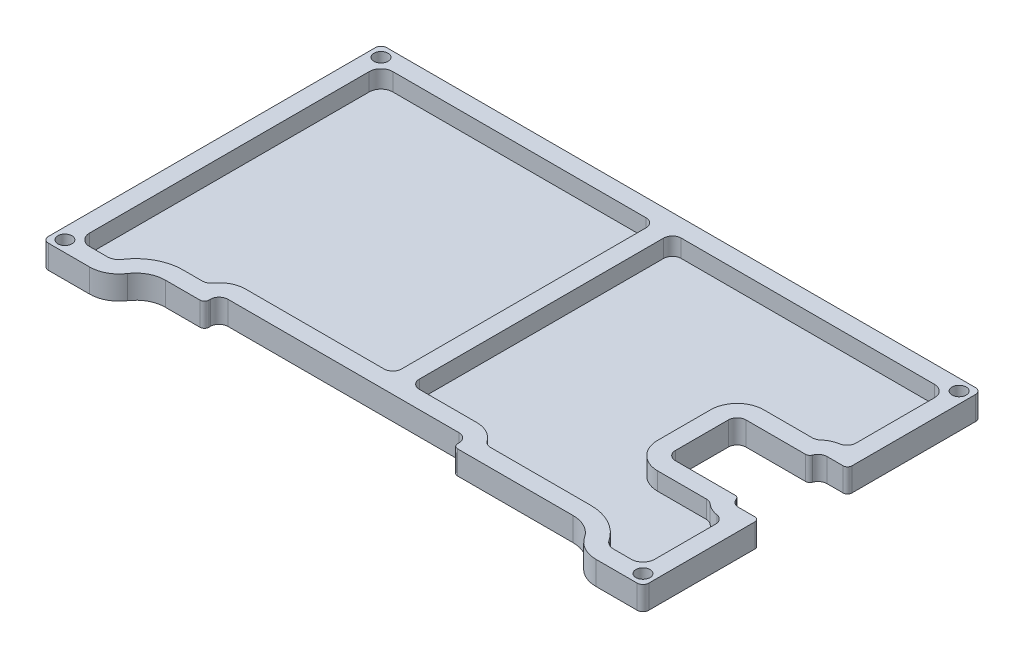
SolidWorks part; units mm, degrees
ref_plane "Ebene vorne" through (0, 0, 0) normal (0, 0, 1) x (1, 0, 0)
ref_plane "Ebene oben" through (0, 0, 0) normal (0, 1, 0) x (1, 0, 0)
ref_plane "Ebene rechts" through (0, 0, 0) normal (1, 0, 0) x (0, 0, -1)
sketch "Skizze1" plane through (0, 0, 0) normal (0, 1, 0) x (1, 0, 0)
  line L1 (-49.1, -26.85) -> (49.1, -26.85) construction
  line L2 (-49.1, -26.85) -> (-49.1, 26.85) construction
  line L3 (-49.1, 26.85) -> (49.1, 26.85) construction
  line L4 (49.1, -26.85) -> (49.1, 26.85) construction
  line L5 (-49.1, -26.85) -> (49.1, 26.85) construction
  line L6 (-49.1, 26.85) -> (49.1, -26.85) construction
  line L7 (-51, -28.75) -> (51, -28.75)
  line L8 (-51, -28.75) -> (-51, 28.75)
  line L9 (-51, 28.75) -> (51, 28.75)
  line L10 (51, -28.75) -> (51, 28.75)
  line L11 (-51, -28.75) -> (51, 28.75) construction
  line L12 (-51, 28.75) -> (51, -28.75) construction
  point P0 (0, 0)
  point P6 (0, 0)
  dimension "D1" = 102
  dimension "D2" = 57.5
  dimension "D3" = 98.2
  dimension "D4" = 53.7
extrude "Aufsatz-Linear austragen1" add sketch "Skizze1" along normal blind 1
fillet "Verrundung1" radius 1 4 edges at (51, 0.5, -28.75) (51, 0.5, 28.75) (-51, 0.5, 28.75) (-51, 0.5, -28.75)
sketch "Skizze5" plane through (0, 1, 0) normal (0, 1, 0) x (1, 0, 0)
  line L0 (-43, -28.75) -> (43, -28.75)
  line L1 (-50, -28.75) -> (50, -28.75) construction
  line L2 (-51, 27.75) -> (-51, -27.75) construction
  line L3 (34.6484, -24.25) -> (-34.6484, -24.25)
  line L4 (51, -27.75) -> (51, 27.75) construction
  arc A0 (-38.8242, -26.5) -> (-43, -28.75) centre (-43, -23.75) cw
  arc A1 (-38.8242, -26.5) -> (-34.6484, -24.25) centre (-34.6484, -29.25) cw
  arc A2 (38.8242, -26.5) -> (34.6484, -24.25) centre (34.6484, -29.25) ccw
  arc A3 (43, -28.75) -> (38.8242, -26.5) centre (43, -23.75) cw
  dimension "D3" = 5
  dimension "D1" = 8
  dimension "D2" = 8
  dimension "D4" = 4.5
extrude "Schnitt-Linear austragen1" cut sketch "Skizze5" against normal up to next
sketch "Skizze6" plane through (0, 1, 0) normal (0, 1, 0) x (1, 0, 0)
  line L0 (14.25, -21.75) -> (-28, -21.75)
  line L2 (-28, -21.75) -> (-28, -24.25)
  line L3 (-28, -24.25) -> (14.25, -24.25)
  line L4 (14.25, -24.25) -> (14.25, -21.75)
  line L5 (51, -27.75) -> (51, 27.75) construction
  line L7 (33.75, 4.5) -> (46, 4.5)
  line L8 (51, 4.5) -> (51, -7.5)
  line L9 (46, -7.5) -> (33.75, -7.5)
  line L10 (33.75, -7.5) -> (33.75, 4.5)
  line L11 (43, -28.75) -> (50, -28.75) construction
  line L12 (-51, 27.75) -> (-51, -27.75) construction
  line L13 (34.6484, -24.25) -> (-34.6484, -24.25) construction
  line L14 (46, -7.5) -> (46, -9)
  line L15 (46, -9) -> (51, -9)
  line L16 (51, -9) -> (51, -7.5)
  line L17 (46, 4.5) -> (46, 6)
  line L18 (46, 6) -> (51, 6)
  line L19 (51, 6) -> (51, 4.5)
  line L20 (46, -7.5) -> (51, -7.5) construction
  line L21 (46, 4.5) -> (51, 4.5) construction
  dimension "D1" = 42.25
  dimension "D2" = 23
  dimension "D3" = 2.5
  dimension "D4" = 21.25
  dimension "D5" = 12
  dimension "D6" = 17.25
  dimension "D7" = 15
  dimension "D8" = 5
extrude "Schnitt-Linear austragen2" cut sketch "Skizze6" against normal up to next
fillet "Verrundung2" radius 1.5 6 edges at (33.75, 0.5, -4.5) (33.75, 0.5, 7.5) (14.25, 0.5, 21.75) (-28, 0.5, 21.75) (46, 0.5, -6) (46, 0.5, 9)
fillet "Verrundung3" radius 0.75 6 edges at (-28, 0.5, 24.25) (14.25, 0.5, 24.25) (51, 0.5, -6) (51, 0.5, 9) (46, 0.5, -4.5) (46, 0.5, 7.5)
sketch "Skizze8" plane through (0, 1, 0) normal (0, 1, 0) x (1, 0, 0)
  line L0 (35.25, 7.5) -> (44.1459, 7.5)
  line L1 (47.5, 9) -> (48, 9)
  line L2 (48, 9) -> (48, 25.75)
  line L3 (48, 25.75) -> (1.5, 25.75)
  line L4 (-48, 25.75) -> (-48, -25.75)
  line L5 (-48, -25.75) -> (-43, -25.75)
  line L6 (-34.6484, -21.25) -> (-30.5311, -21.25)
  line L7 (-30.5311, -21.25) -> (-30.5311, -21.25)
  line L8 (-26.5, -18.75) -> (-1.5, -18.75)
  line L9 (16.7811, -21.25) -> (16.7811, -21.25)
  line L10 (16.7811, -21.25) -> (34.6484, -21.25)
  line L11 (43, -25.75) -> (48, -25.75)
  line L12 (48, -25.75) -> (48, -12)
  line L13 (48, -12) -> (47.5, -12)
  line L14 (44.1459, -10.5) -> (35.25, -10.5)
  line L15 (30.75, -6) -> (30.75, 3)
  line L16 (35.25, 4.5) -> (45.3787, 4.5)
  line L17 (47.5, 6) -> (50.25, 6)
  line L18 (51, 6.75) -> (51, 27.75)
  line L19 (50, 28.75) -> (-50, 28.75)
  line L20 (-51, 27.75) -> (-51, -27.75)
  line L21 (-50, -28.75) -> (-43, -28.75)
  line L22 (-34.6484, -24.25) -> (-28.75, -24.25)
  line L23 (-28, -23.5) -> (-28, -23.25)
  line L24 (-26.5, -21.75) -> (12.75, -21.75)
  line L25 (14.25, -23.25) -> (14.25, -23.5)
  line L26 (15, -24.25) -> (34.6484, -24.25)
  line L27 (43, -28.75) -> (50, -28.75)
  line L28 (51, -27.75) -> (51, -9.75)
  line L29 (50.25, -9) -> (47.5, -9)
  line L30 (45.3787, -7.5) -> (35.25, -7.5)
  line L31 (33.75, -6) -> (33.75, 3)
  line L32 (35.25, 4.5) -> (45.3787, 4.5)
  line L33 (47.5, 6) -> (50.25, 6)
  line L34 (51, 6.75) -> (51, 27.75)
  line L35 (50, 28.75) -> (-50, 28.75)
  line L36 (-51, 27.75) -> (-51, -27.75)
  line L37 (-50, -28.75) -> (-43, -28.75)
  line L38 (-34.6484, -24.25) -> (-28.75, -24.25)
  line L39 (-28, -23.5) -> (-28, -23.25)
  line L40 (-26.5, -21.75) -> (12.75, -21.75)
  line L41 (14.25, -23.25) -> (14.25, -23.5)
  line L42 (15, -24.25) -> (34.6484, -24.25)
  line L43 (43, -28.75) -> (50, -28.75)
  line L44 (51, -27.75) -> (51, -9.75)
  line L45 (50.25, -9) -> (47.5, -9)
  line L46 (45.3787, -7.5) -> (35.25, -7.5)
  line L47 (33.75, -6) -> (33.75, 3)
  line L48 (-1.5, 25.75) -> (-1.5, -18.75)
  line L49 (1.5, 0) -> (0, 0) construction
  line L50 (0, 0) -> (-1.5, 0) construction
  line L51 (1.5, 25.75) -> (1.5, -18.75)
  line L52 (1.5, -18.75) -> (12.75, -18.75)
  line L53 (-26.5, -18.75) -> (12.75, -18.75) construction
  line L54 (-1.5, 25.75) -> (-48, 25.75)
  line L55 (48, 25.75) -> (-48, 25.75) construction
  arc A0 (44.1459, 7.5) -> (44.1459, 7.5) centre (44.1459, 7.5) ccw
  arc A1 (47.5, 9) -> (44.1459, 7.5) centre (47.5, 4.5) ccw
  arc A2 (48, 9) -> (48, 9) centre (48, 9) ccw
  arc A3 (48, 25.75) -> (48, 25.75) centre (48, 25.75) ccw
  arc A4 (-48, 25.75) -> (-48, 25.75) centre (-48, 25.75) ccw
  arc A5 (-48, -25.75) -> (-48, -25.75) centre (-48, -25.75) ccw
  arc A6 (-43, -25.75) -> (-41.3297, -24.85) centre (-43, -23.75) ccw
  arc A7 (-34.6484, -21.25) -> (-41.3297, -24.85) centre (-34.6484, -29.25) ccw
  arc A8 (-30.5311, -21.25) -> (-30.5311, -21.25) centre (-30.5311, -21.25) ccw
  arc A9 (-26.5, -18.75) -> (-30.5311, -21.25) centre (-26.5, -23.25) ccw
  arc A10 (16.7811, -21.25) -> (12.75, -18.75) centre (12.75, -23.25) ccw
  arc A11 (16.7811, -21.25) -> (16.7811, -21.25) centre (16.7811, -21.25) ccw
  arc A12 (41.3297, -24.85) -> (34.6484, -21.25) centre (34.6484, -29.25) ccw
  arc A13 (41.3297, -24.85) -> (43, -25.75) centre (43, -23.75) ccw
  arc A14 (48, -25.75) -> (48, -25.75) centre (48, -25.75) ccw
  arc A15 (48, -12) -> (48, -12) centre (48, -12) ccw
  arc A16 (44.1459, -10.5) -> (47.5, -12) centre (47.5, -7.5) ccw
  arc A17 (44.1459, -10.5) -> (44.1459, -10.5) centre (44.1459, -10.5) ccw
  arc A18 (30.75, -6) -> (35.25, -10.5) centre (35.25, -6) ccw
  arc A19 (35.25, 7.5) -> (30.75, 3) centre (35.25, 3) ccw
  arc A20 (45.3787, 4.5) -> (46.0858, 5) centre (45.3787, 5.25) ccw
  arc A21 (47.5, 6) -> (46.0858, 5) centre (47.5, 4.5) ccw
  arc A22 (50.25, 6) -> (51, 6.75) centre (50.25, 6.75) ccw
  arc A23 (51, 27.75) -> (50, 28.75) centre (50, 27.75) ccw
  arc A24 (-50, 28.75) -> (-51, 27.75) centre (-50, 27.75) ccw
  arc A25 (-51, -27.75) -> (-50, -28.75) centre (-50, -27.75) ccw
  arc A26 (-43, -28.75) -> (-38.8242, -26.5) centre (-43, -23.75) ccw
  arc A27 (-34.6484, -24.25) -> (-38.8242, -26.5) centre (-34.6484, -29.25) ccw
  arc A28 (-28.75, -24.25) -> (-28, -23.5) centre (-28.75, -23.5) ccw
  arc A29 (-26.5, -21.75) -> (-28, -23.25) centre (-26.5, -23.25) ccw
  arc A30 (14.25, -23.25) -> (12.75, -21.75) centre (12.75, -23.25) ccw
  arc A31 (14.25, -23.5) -> (15, -24.25) centre (15, -23.5) ccw
  arc A32 (38.8242, -26.5) -> (34.6484, -24.25) centre (34.6484, -29.25) ccw
  arc A33 (38.8242, -26.5) -> (43, -28.75) centre (43, -23.75) ccw
  arc A34 (50, -28.75) -> (51, -27.75) centre (50, -27.75) ccw
  arc A35 (51, -9.75) -> (50.25, -9) centre (50.25, -9.75) ccw
  arc A36 (46.0858, -8) -> (47.5, -9) centre (47.5, -7.5) ccw
  arc A37 (46.0858, -8) -> (45.3787, -7.5) centre (45.3787, -8.25) ccw
  arc A38 (33.75, -6) -> (35.25, -7.5) centre (35.25, -6) ccw
  arc A39 (35.25, 4.5) -> (33.75, 3) centre (35.25, 3) ccw
  arc A40 (45.3787, 4.5) -> (46.0858, 5) centre (45.3787, 5.25) ccw
  arc A41 (47.5, 6) -> (46.0858, 5) centre (47.5, 4.5) ccw
  arc A42 (50.25, 6) -> (51, 6.75) centre (50.25, 6.75) ccw
  arc A43 (51, 27.75) -> (50, 28.75) centre (50, 27.75) ccw
  arc A44 (-50, 28.75) -> (-51, 27.75) centre (-50, 27.75) ccw
  arc A45 (-51, -27.75) -> (-50, -28.75) centre (-50, -27.75) ccw
  arc A46 (-43, -28.75) -> (-38.8242, -26.5) centre (-43, -23.75) ccw
  arc A47 (-34.6484, -24.25) -> (-38.8242, -26.5) centre (-34.6484, -29.25) ccw
  arc A48 (-28.75, -24.25) -> (-28, -23.5) centre (-28.75, -23.5) ccw
  arc A49 (-26.5, -21.75) -> (-28, -23.25) centre (-26.5, -23.25) ccw
  arc A50 (14.25, -23.25) -> (12.75, -21.75) centre (12.75, -23.25) ccw
  arc A51 (14.25, -23.5) -> (15, -24.25) centre (15, -23.5) ccw
  arc A52 (38.8242, -26.5) -> (34.6484, -24.25) centre (34.6484, -29.25) ccw
  arc A53 (38.8242, -26.5) -> (43, -28.75) centre (43, -23.75) ccw
  arc A54 (50, -28.75) -> (51, -27.75) centre (50, -27.75) ccw
  arc A55 (51, -9.75) -> (50.25, -9) centre (50.25, -9.75) ccw
  arc A56 (46.0858, -8) -> (47.5, -9) centre (47.5, -7.5) ccw
  arc A57 (46.0858, -8) -> (45.3787, -7.5) centre (45.3787, -8.25) ccw
  arc A58 (33.75, -6) -> (35.25, -7.5) centre (35.25, -6) ccw
  arc A59 (35.25, 4.5) -> (33.75, 3) centre (35.25, 3) ccw
  dimension "D3" = 3
  dimension "D1" = 0
  dimension "D2" = 3
extrude "Aufsatz-Linear austragen2" add sketch "Skizze8" along normal blind 3
fillet "Verrundung4" radius 2 4 edges at (48, 2.5, -25.75) (48, 2.5, 25.75) (-48, 2.5, 25.75) (-48, 2.5, -25.75)
hole_wizard "Durchgangsloch für M21" positions "Skizze4" profile "Skizze2" hole size "M2" standard "DIN" end condition up to next
sketch "Skizze4" plane through (0, 0, 0) normal (0, -1, 0) x (-1, 0, 0)
  line L1 (49.1, 26.85) -> (-49.1, 26.85)
  line L2 (49.1, 26.85) -> (49.1, -26.85)
  line L3 (49.1, -26.85) -> (-49.1, -26.85)
  line L4 (-49.1, 26.85) -> (-49.1, -26.85)
  line L5 (49.1, 26.85) -> (-49.1, -26.85) construction
  line L6 (49.1, -26.85) -> (-49.1, 26.85) construction
  point P2 (-49.1, -26.85)
  point P107 (49.1, 26.85)
  point P108 (49.1, -26.85)
  point P109 (-49.1, 26.85)
  dimension "D1" = 98.2
  dimension "D2" = 53.7
sketch "Skizze2" plane through (49.1, 0, 26.85) normal (1, 0, 0) x (0, 0, -1)
  line L0 (0, 0) -> (0, 4)
  line L1 (0, 4) -> (1.2, 4)
  line L2 (1.2, 4) -> (1.2, 0)
  line L5 (1.2, 0) -> (0, 0)
  line L11 (0, -6.35) -> (0, 107.95) construction
  dimension "Bohrerdurchmesser" = 2.4
  dimension "Bohrungstiefe" = 4
fillet "Verrundung5" radius 1.5 10 edges at (-30.5311, 2.5, 21.25) (-1.5, 2.5, -25.75) (-1.5, 2.5, 18.75) (1.5, 2.5, 18.75) (1.5, 2.5, -25.75) (48, 2.5, -9) (44.1459, 2.5, -7.5) (44.1459, 2.5, 10.5) (48, 2.5, 12) (16.7811, 2.5, 21.25)
